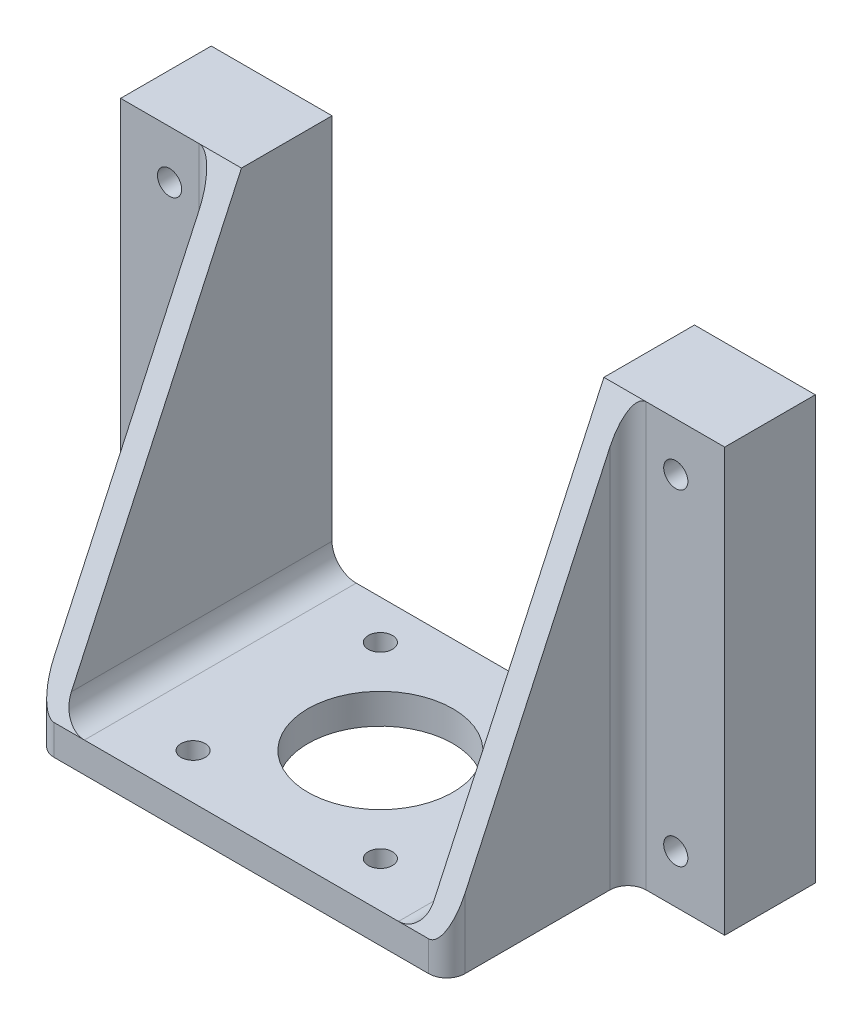
SolidWorks part; units mm, degrees
ref_plane "前视基准面" through (0, 0, 0) normal (0, 0, 1) x (1, 0, 0)
ref_plane "上视基准面" through (0, 0, 0) normal (0, 1, 0) x (1, 0, 0)
ref_plane "右视基准面" through (0, 0, 0) normal (1, 0, 0) x (0, 0, -1)
other "Configuration Table"
sketch "草图5" plane through (0, 0, 0) normal (0, 0, 1) x (1, 0, 0)
  line L0 (-41.9, 0) -> (0, 0)
  line L1 (-50, 35) -> (50, 35)
  line L2 (-50, 35) -> (-50, -35)
  line L3 (-50, -35) -> (50, -35)
  line L4 (50, 35) -> (50, -35)
  line L5 (-50, 35) -> (50, -35) construction
  line L6 (-50, -35) -> (50, 35) construction
  line L7 (-41.9, 27) -> (41.9, 27)
  line L8 (-41.9, 27) -> (-41.9, -27)
  line L9 (-41.9, -27) -> (41.9, -27)
  line L10 (41.9, 27) -> (41.9, -27)
  line L11 (-41.9, 27) -> (41.9, -27) construction
  line L12 (-41.9, -27) -> (41.9, 27) construction
  line L13 (0, 0) -> (0, 27)
  line L15 (-21, 35) -> (21, 35)
  line L17 (-21, -27) -> (21, -27)
  circle A0 centre (-41.9, 27) radius 2
  circle A1 centre (41.9, 27) radius 2
  circle A2 centre (41.9, -27) radius 2
  circle A3 centre (-41.9, -27) radius 2
  point P0 (0, 0)
  point P6 (0, 0)
  point P18 (0, 4)
  dimension "D5" = 0
  dimension "D1" = 100
  dimension "D2" = 70
  dimension "D3" = 8.1
  dimension "D4" = 8
extrude "凸台-拉伸10" add sketch "草图5" along normal blind 0.0001 contours L4 L1 L2 L3 L9 A3 L8 A0 L7 A1 L10 A2 | A0 L8 L0 L13 L7 | L8 A3 L9 A2 L10 A1 L7 L13 L0 region at (-20.894, 13.4648, 0) region at (6.9647, -4.4883, 0) region at (-35.5, 33.7793, 0)
sketch "草图6" plane through (0, 0, 0.0001) normal (0, 0, 1) x (1, 0, 0)
  line L0 (-50, -35) -> (50, -35) construction
  line L1 (-30, -30) -> (30, -30)
  line L2 (-30, -30) -> (-30, -35)
  line L3 (-30, -35) -> (30, -35)
  line L4 (30, -30) -> (30, -35)
  line L5 (-30, -30) -> (30, -35) construction
  line L6 (-30, -35) -> (30, -30) construction
  line L7 (0, -30) -> (0, -35)
  point P0 (0, -32.5)
  dimension "D1" = 60
  dimension "D2" = 5
extrude "凸台-拉伸11" add sketch "草图6" along normal blind 45 contours L1 L7 L3 L4 | L1 L4 L3 L2 region at (15, -32.5, 0.0001)
sketch "草图7" plane through (0, 0, 0.0001) normal (0, 0, 1) x (1, 0, 0)
  line L0 (0, 0) -> (0, -27)
  line L1 (-30, -35) -> (-34, -35)
  line L2 (-30, -35) -> (-30, 35)
  line L3 (-30, 35) -> (-34, 35)
  line L4 (-34, -35) -> (-34, 35)
  line L6 (30, 35) -> (34, 35)
  line L7 (34, -35) -> (34, 35)
  line L8 (30, -35) -> (34, -35)
  line L9 (30, -35) -> (30, 35)
  line M11 (30, -30) -> (30, -35)
  line M12 (30, -35) -> (50, -35)
  line M20 (-50, -35) -> (-30, -35)
  line M21 (-30, -35) -> (-30, -30)
  dimension "D1" = 4
  dimension "D2" = 70
extrude "凸台-拉伸12" add sketch "草图7" along normal blind 45 contours L4 L2 L3 M20 M21 | L9 L7 L6 M11 M12 region at (-32, 0, 0.0001) region at (32, 0, 0.0001)
sketch "草图8" plane through (-34, 0, 0) normal (-1, 0, 0) x (0, 0, 1)
  line L0 (45.0001, -30) -> (15.0001, 35)
  line L2 (15.0001, 35) -> (45.0001, 35)
  line L3 (45.0001, 35) -> (45.0001, -30)
  line L4 (45.0001, -35) -> (45.0001, 35) construction
  line L5 (45.0001, 35) -> (0.0001, 35) construction
  dimension "D1" = 0
  dimension "D2" = 15
extrude "切除-拉伸1" cut sketch "草图8" against normal blind 76
sketch "草图16" plane through (0, 0, 0.0001) normal (0, 0, 1) x (1, 0, 0)
  line L4 (50, 35) -> (34, 35)
  line L5 (34, 35) -> (34, -35)
  line L6 (34, -35) -> (50, -35)
  line L7 (50, -35) -> (50, 35)
  line L8 (50, 35) -> (34, 35)
  line L9 (34, 35) -> (34, -35)
  line L10 (34, -35) -> (50, -35)
  line L11 (50, -35) -> (50, 35)
  line L12 (-34, -35) -> (-34, 35)
  line L13 (-34, 35) -> (-50, 35)
  line L14 (-50, 35) -> (-50, -35)
  line L15 (-50, -35) -> (-34, -35)
  line L16 (-34, -35) -> (-34, 35)
  line L17 (-34, 35) -> (-50, 35)
  line L18 (-50, 35) -> (-50, -35)
  line L19 (-50, -35) -> (-34, -35)
  circle A1 centre (-41.9, 27) radius 2
  circle A3 centre (-41.9, -27) radius 2
  circle A4 centre (41.9, 27) radius 2 construction
  circle A5 centre (41.9, -27) radius 2 construction
  circle A6 centre (41.9, 27) radius 2
  circle A7 centre (41.9, -27) radius 2
  dimension "D1" = 0
  dimension "D2" = 0
extrude "凸台-拉伸16" add sketch "草图16" along normal blind 15 contours L8 L9 L10 L11 | L16 L17 L18 L19
extrude "切除-拉伸2" cut sketch "草图5<3>" along normal blind 49 contours L7 A0 L8 | L8 A0 L7 | A1 L10 L7 | A1 L7 L10 | L9 A2 L10 | L10 A2 L9 | A3 L9 L8 | A3 L8 L9 region at (-42.1829, 27.2829, 0) region at (-41.0512, 26.1512, 0) region at (-41.0512, -26.1512, 0) region at (-42.1829, -27.2829, 0) region at (42.1829, 27.2829, 0) region at (41.0512, 26.1512, 0) region at (42.1829, -27.2829, 0) region at (41.0512, -26.1512, 0)
sketch "草图5<3>" plane through (0, 0, 0) normal (0, 0, 1) x (1, 0, 0) same geometry as "草图5"
sketch "草图17" plane through (0, -35, 0) normal (0, -1, 0) x (1, 0, 0)
  line L1 (-15.5, 37.5) -> (15.5, 37.5)
  line L2 (-15.5, 37.5) -> (-15.5, 6.5)
  line L3 (-15.5, 6.5) -> (15.5, 6.5)
  line L4 (15.5, 37.5) -> (15.5, 6.5)
  line L5 (-15.5, 37.5) -> (15.5, 6.5)
  line L6 (15.5, 37.5) -> (-15.5, 6.5)
  line L7 (-15.5, 22) -> (0, 22)
  line L8 (0, 22) -> (0, 37.5)
  line L9 (-50, 0) -> (50, 0) construction
  circle A0 centre (-15.5, 37.5) radius 2
  circle A1 centre (15.5, 37.5) radius 2
  circle A2 centre (-15.5, 6.5) radius 2
  circle A3 centre (15.5, 6.5) radius 2
  circle A4 centre (0, 22) radius 12
  dimension "D4" = 24
  dimension "D1" = 6.5
  dimension "D2" = 31
  dimension "D3" = 31
extrude "切除-拉伸5" cut sketch "草图17" against normal through all contours L5 A4 L7 | L8 A4 L5 | L5 A4 L6 | L6 A4 L8 | L6 A4 L5 | L7 A4 L6 | A3 | A2 | A0 | A1 region at (-2.9834, -35, 29.2025) region at (-7.2025, -35, 24.9834) region at (2.9834, -35, 29.2025) region at (-7.2025, -35, 19.0166) region at (7.2025, -35, 22) region at (0, -35, 14.7975)
fillet "圆角1" radius 3 4 edges at (34, 0, 15.0001) (-34, 0, 15.0001) (-34, -32.5, 45.0001) (34, -32.5, 45.0001)
sketch "草图18" plane through (0, 0, 0.0001) normal (0, 0, 1) x (1, 0, 0)
  line L4 (30, -30) -> (30, 35)
  line L5 (30, 35) -> (-30, 35)
  line L6 (-30, 35) -> (-30, -30)
  line L7 (-30, -30) -> (30, -30)
  line L8 (30, -30) -> (30, 35)
  line L9 (30, 35) -> (-30, 35)
  line L10 (-30, 35) -> (-30, -30)
  line L11 (-30, -30) -> (30, -30)
  dimension "D1" = 0
extrude "切除-拉伸6" cut sketch "草图18" against normal through all
fillet "圆角2" radius 4 2 edges at (-30, -30, 22.5001) (30, -30, 22.5001)
